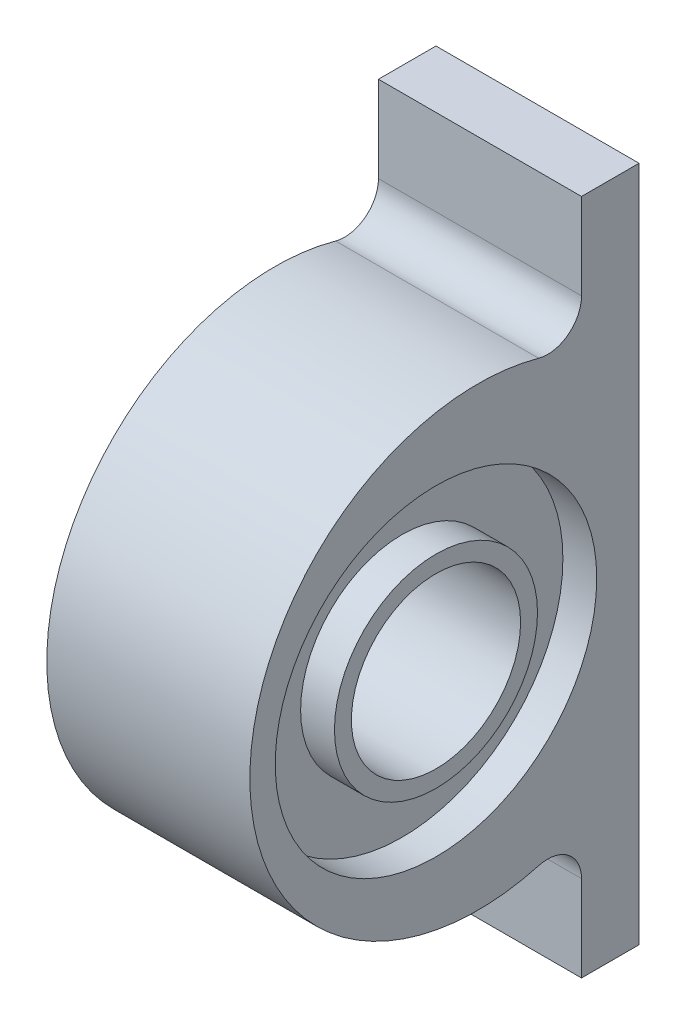
SolidWorks part; units mm, degrees
ref_plane "Front Plane" through (0, 0, 0) normal (0, 0, 1) x (1, 0, 0)
ref_plane "Top Plane" through (0, 0, 0) normal (0, 1, 0) x (1, 0, 0)
ref_plane "Right Plane" through (0, 0, 0) normal (1, 0, 0) x (0, 0, -1)
sketch "Sketch1" plane through (0, 0, 0) normal (1, 0, 0) x (0, 0, -1)
  line L0 (0, -100) -> (0, 100)
  line L1 (0, 100) -> (-17, 100)
  line L2 (-17, 100) -> (-17, 60)
  line L3 (-17, -100) -> (0, -100)
  line L4 (-17, -60) -> (-17, -100)
  arc A0 (-17, 60) -> (-17, -60) centre (-47.6327, 0) ccw
  point P4 (0, 0)
  point P9 (-115, 0)
  point P10 (0, 0)
  dimension "D1" = 200
  dimension "D2" = 115
  dimension "D3" = 17
  dimension "D4" = 120
extrude "Boss-Extrude1" add sketch "Sketch1" along normal mid plane 60
fillet "Fillet1" radius 10 2 edges at (0, -60, 17) (0, 60, 17)
sketch "Sketch2" plane through (0, 0, 0) normal (1, 0, 0) x (0, 0, -1)
  line L1 (0, -100) -> (0, 100) construction
  circle A0 centre (-60, 0) radius 25
  point P3 (0, 0)
  dimension "D1" = 85
  dimension "D2" = 50
extrude "Cut-Extrude1" cut sketch "Sketch2" against normal through all both and the other way through all
sketch "Sketch3" plane through (0, 0, 0) normal (1, 0, 0) x (0, 0, -1)
  circle A0 centre (-60, 0) radius 47.5
  dimension "D1" = 95
extrude "Cut-Extrude2" cut sketch "Sketch3" along normal blind 10 from surface starting at face at (-30, 0, 35)
extrude "Cut-Extrude3" cut sketch "Sketch3<3>" against normal blind 10 from surface starting at face at (30, 0, 35)
sketch "Sketch3<3>" plane through (0, 0, 0) normal (1, 0, 0) x (0, 0, -1) same geometry as "Sketch3"
sketch "Sketch4" plane through (0, 0, 0) normal (1, 0, 0) x (0, 0, -1)
  circle A0 centre (-60, 0) radius 25 construction
  circle A1 centre (-60, 0) radius 25
  circle A2 centre (-60, 0) radius 30
  dimension "D1" = 60
extrude "Boss-Extrude2" add sketch "Sketch4" along normal through all and the other way through all
